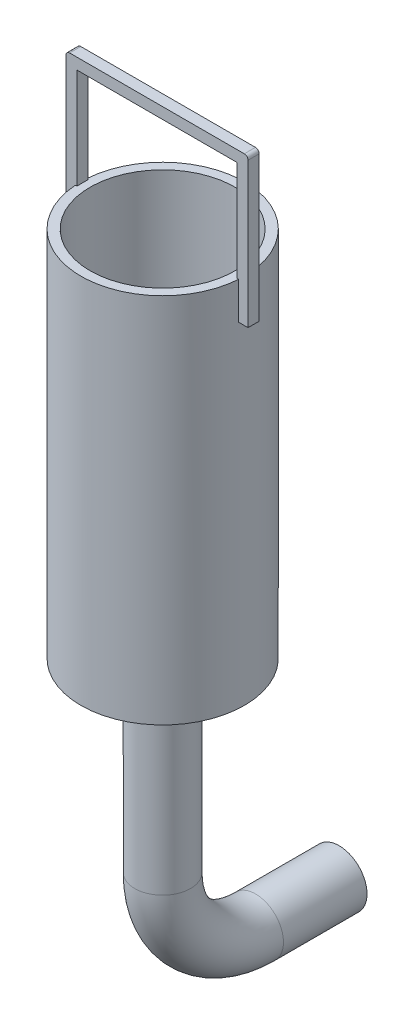
SolidWorks part; units mm, degrees
ref_plane "Plano frontal" through (0, 0, 0) normal (0, 0, 1) x (1, 0, 0)
ref_plane "Plano superior" through (0, 0, 0) normal (0, 1, 0) x (1, 0, 0)
ref_plane "Plano direito" through (0, 0, 0) normal (1, 0, 0) x (0, 0, -1)
sketch "Esboço1" plane through (0, 0, 0) normal (0, 1, 0) x (1, 0, 0)
  circle A0 centre (0, 0) radius 44
extrude "Ressalto-extrusão1" add sketch "Esboço1" along normal blind 200
sketch "Esboço2" plane through (0, 200, 0) normal (0, 1, 0) x (1, 0, 0)
  circle A0 centre (0, 0) radius 39
extrude "Corte-extrusão1" cut sketch "Esboço2" against normal blind 192
sketch "Esboço3" plane through (0, 8, 0) normal (0, 1, 0) x (1, 0, 0)
  circle A0 centre (0, 0) radius 15.7
extrude "Corte-extrusão2" cut sketch "Esboço3" against normal up to next
sketch "Esboço4" plane through (0, 0, 0) normal (0, 0, 1) x (1, 0, 0)
  line L0 (-49.0407, 200) -> (-49.0407, 260)
  line L1 (-49.0407, 260) -> (48.9428, 260)
  line L2 (48.9428, 260) -> (48.9428, 200)
  line L3 (48.9428, 200) -> (39, 200)
  line L4 (-43.0407, 200) -> (-43.0407, 254)
  line L5 (-43.0407, 254) -> (42.9428, 254)
  line L6 (42.9428, 254) -> (42.9428, 200)
  line L7 (-49.0407, 200) -> (-43.0407, 200)
  line L8 (-44, 200) -> (-44, 0) construction
  line L9 (-49.0407, 200) -> (-44, 200)
  line L10 (-49.0407, 200) -> (-49.0407, 180)
  line L11 (-49.0407, 180) -> (-44, 180)
  line L13 (44, 0) -> (44, 200) construction
  line L14 (48.9428, 200) -> (44, 200)
  line L15 (48.9428, 200) -> (48.9428, 180)
  line L16 (48.9428, 180) -> (44, 180)
  line L17 (44, 200) -> (44, 180)
  line L19 (-43.0407, 200) -> (-49.0407, 200)
  line L20 (-43.0407, 200) -> (-43.0407, 180)
  line L21 (-43.0407, 180) -> (-49.0407, 180)
  line L22 (-49.0407, 200) -> (-49.0407, 180)
  line L23 (48.9428, 200) -> (42.9428, 200)
  line L24 (48.9428, 200) -> (48.9428, 180)
  line L25 (48.9428, 180) -> (42.9428, 180)
  line L26 (42.9428, 200) -> (42.9428, 180)
  dimension "D1" = 6
extrude "Ressalto-extrusão2" add sketch "Esboço4" along normal blind 3 and the other way blind 3 contours L0 L7 L4 L5 L6 L3 L2 L1 | L21 L20 L7 L10 L11 | L3 L17 L16 L15 | L3 L26 L25 L17 region at (-47.8918, 230, 0) region at (-46.0407, 190, 0) region at (46.4714, 190, 0) region at (43.4714, 190, 0)
fillet "Filete1" radius 2 2 edges at (-49.0407, 260, 0) (48.9428, 260, 0)
sketch3d "3DSketch1"
  line L0 (0, -149.8108, -132.3074) -> (0, -149.8108, -94.9506) construction
  line L1 (0, 0, 0) -> (0, -149.8108, 0) construction
  line L2 (0, -149.8108, 0) -> (0, -149.8108, -132.3074) construction
  line L3 (0, 0, 0) -> (0, -99.8108, 0)
  line L4 (0, -149.8108, -50) -> (0, -149.8108, -94.9506)
  line L5 (0, -149.8108, -94.9506) -> (41.2196, -149.8108, -94.9506) construction
  line L6 (0, -149.8108, 0) -> (51.0081, -149.8108, 0) construction
  arc A1 (0, -149.8108, -50) -> (0, -99.8108, 0) centre (0, -99.8108, -50) ccw
  circle A2 centre (0, -149.8108, -94.9506) radius 50 construction
  point P4 (0, -149.8108, 0)
  point P9 (-50, -99.8108, -50)
  point P14 (0, -149.8108, -144.9506)
  dimension "D1" = 50
sweep "Sweep-Thin1" add path "3DSketch1" circular profile diameter 30 parameters "D1"=1, "D3"=30
